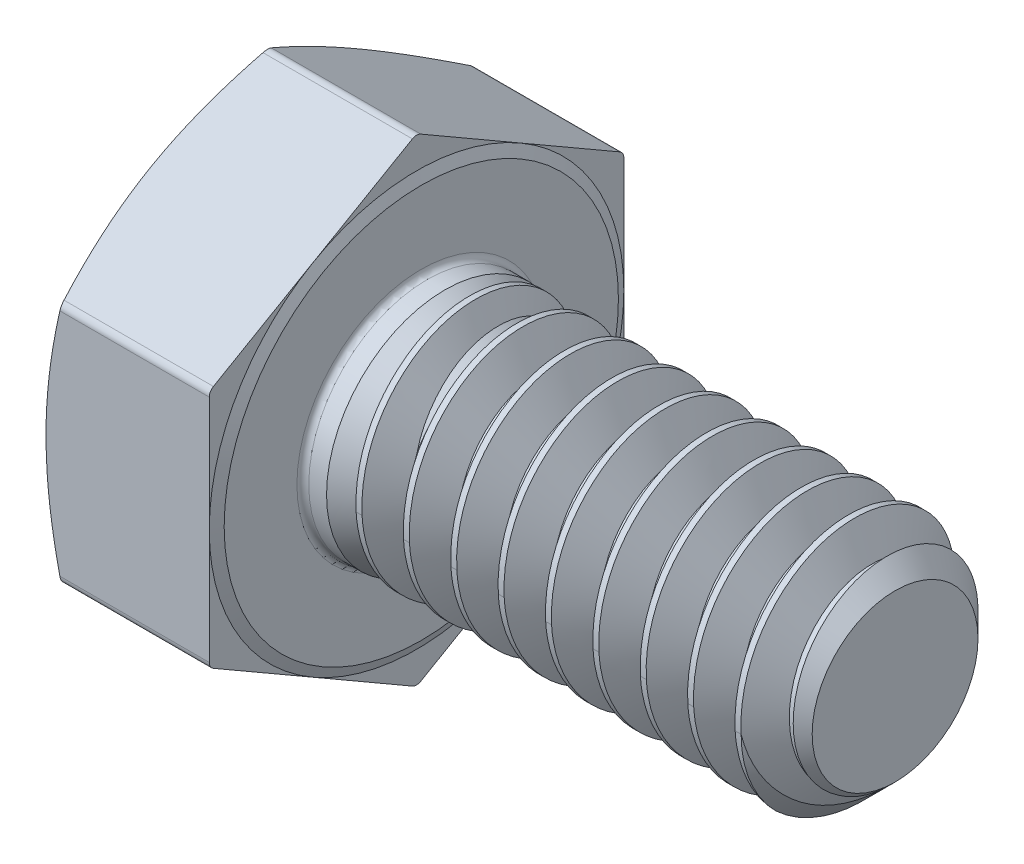
SolidWorks part; units mm, degrees
material "Plain Carbon Steel"
ref_plane "Front Plane" through (0, 0, 0) normal (0, 0, 1) x (1, 0, 0)
ref_plane "Top Plane" through (0, 0, 0) normal (0, 1, 0) x (1, 0, 0)
ref_plane "Right Plane" through (0, 0, 0) normal (1, 0, 0) x (0, 0, -1)
sketch "Sketch1" plane through (0, 0, 0) normal (0, 0, 1) x (1, 0, 0)
  line L0 (0, 0) -> (12.7, 0) construction
  line L1 (0, 0) -> (-4.7625, 0) construction
  line L2 (0, 5.5562) -> (0, -5.5562) construction
  line L3 (-4.7625, 5.5562) -> (-4.7625, -5.5563) construction
  line L4 (12.7, 3.175) -> (12.7, -3.175) construction
  line L8 (11.43, 3.175) -> (12.7, 3.175) construction
  point P8 (11.43, 0)
  point P11 (8.255, -3.175)
  point P12 (0.635, 0)
  dimension "Head Height" = 4.7625
  dimension "Head Width" = 11.1125
  dimension "Length" = 12.7
  dimension "Thread Size" = 6.35
  dimension "D1" = 4.445
  dimension "Thread Pitch" = 1.27
  dimension "D2" = 0.635
sketch "Sketch2" plane through (0, 0, 0) normal (1, 0, 0) x (0, 0, -1)
  circle A0 centre (0, 0) radius 3.175
extrude "Boss-Extrude1" add sketch "Sketch2" along normal up to vertex (12.7 mm away) up to point (12.7, 3.175, 0)
sketch "Sketch3" plane through (0, 0, 0) normal (-1, 0, 0) x (0, 0, 1)
  line L0 (0, 6.4158) -> (0, 0) construction
  line L1 (0, 6.4158) -> (-5.5563, 3.2079)
  line L2 (-5.5563, 3.2079) -> (-5.5562, -3.2079)
  line L3 (-5.5562, -3.2079) -> (0, -6.4158)
  line L4 (0, -6.4158) -> (5.5563, -3.2079)
  line L5 (5.5563, -3.2079) -> (5.5563, 3.2079)
  line L6 (5.5563, 3.2079) -> (0, 6.4158)
  circle A0 centre (0, 0) radius 5.5562 construction
extrude "Boss-Extrude2" add sketch "Sketch3" along normal up to vertex (4.7625 mm away) up to point (-4.7625, 5.5562, 0)
sketch "Sketch5" plane through (-4.7625, 0, 0) normal (-1, 0, 0) x (0, 0, 1)
  circle A0 centre (0, 0) radius 5.5562 construction
  circle A1 centre (0, 0) radius 5.5562 construction
  circle A2 centre (0, 0) radius 5.0006
  dimension "D1" = 0.5556
extrude "Cut-Extrude1" cut sketch "Sketch5" against normal up to vertex (4.7625 mm away) draft 65 flip side to cut up to point (0, 0, 0)
sketch "Sketch11" plane through (-4.7625, 0, 0) normal (-1, 0, 0) x (0, 0, 1)
  line L0 (0, 4.6672) -> (0, 2.9726) construction
  line L1 (0.1945, 4.6672) -> (0.1945, 2.9726)
  line L2 (-0.1945, 4.6672) -> (-0.1945, 2.9726)
  arc A0 (0.1945, 4.6672) -> (-0.1945, 4.6672) centre (0, 4.6672) ccw
  arc A1 (-0.1945, 2.9726) -> (0.1945, 2.9726) centre (0, 2.9726) ccw
  circle A2 centre (0, 0) radius 4.8617 construction
  circle A3 centre (0, 0) radius 2.7781 construction
  point P3 (0, 3.8199)
  dimension "D1" = 9.7234
  dimension "D2" = 5.5562
  dimension "D3" = 0.3889
extrude "Boss-Extrude5" add sketch "Sketch11" along normal blind 0.0635
fillet "Fillet5" radius 0.0635 4 edges at (-4.826, 3.8199, 0.1945) (-4.826, 2.7781, 0) (-4.826, 3.8199, -0.1945) (-4.826, 4.8617, 0)
fillet "Fillet6" radius 0.0635 4 edges at (-4.7625, 2.7781, 0) (-4.7625, 3.8199, -0.1945) (-4.7625, 4.8617, 0) (-4.7625, 3.8199, 0.1945)
pattern_circular "CirPattern1" count 9 over 360 about axis through (0, 0, 0) along (-1, 0, 0) of "Boss-Extrude5", "Fillet5", "Fillet6" reverse direction yes
sketch "Sketch16" plane through (-4.7625, 0, 0) normal (-1, 0, 0) x (0, 0, 1)
  circle A0 centre (0, 0) radius 2.5003
  dimension "D1" = 5.0006
extrude "Cut-Extrude2" cut sketch "Sketch16" against normal blind 0.508 draft 60
fillet "Fillet7" radius 0.2223 6 edges at (-2.0513, -6.4158, 0) (-2.0513, -3.2079, -5.5562) (-2.0513, 3.2079, -5.5563) (-2.0513, 6.4158, 0) (-2.0513, -3.2079, 5.5563) (-2.0513, 3.2079, 5.5563)
chamfer "Chamfer1" distance 0.9525 angle 45 1 edges at (12.7, 0, -3.175)
sketch "Sketch15" plane through (0, 0, 0) normal (0, 0, 1) x (1, 0, 0)
  line L0 (0, 5.2839) -> (-0.127, 5.5562)
  line L1 (0, 5.5562) -> (0, -5.5562) construction
  line L2 (-0.127, 5.5562) -> (-0.127, 6.4158)
  line L3 (-0.127, 6.4158) -> (0, 6.4158)
  line L4 (0, 6.4158) -> (0, 5.2839)
  dimension "D1" = 0.127
  dimension "D2" = 25
revolve "Cut-Revolve1" cut sketch "Sketch15" angle 360 about L1
fillet "Fillet4" radius 0.1588 1 edges at (0, 0, 3.175)
sketch "Reference Sketch1" plane through (0, 0, 0) normal (1, 0, 0) x (0, 0, -1)
  line L1 (0, 6.4158) -> (-5.5562, 3.2079)
  line L2 (-5.5562, 3.2079) -> (-5.5562, -3.2079)
  line L3 (-5.5562, -3.2079) -> (0, -6.4158)
  line L4 (0, -6.4158) -> (5.5562, -3.2079)
  line L5 (5.5562, -3.2079) -> (5.5562, 3.2079)
  line L6 (5.5562, 3.2079) -> (0, 6.4158)
  circle A0 centre (0, 0) radius 5.5562 construction
  circle A1 centre (0, 0) radius 5.5562
sketch "Sketch12" plane through (12.7, 0, 0) normal (1, 0, 0) x (0, 0, -1)
  circle A1 centre (0, 0) radius 3.175
ref_plane "Plane2" through (0.635, 0, 0) normal (1, 0, 0) x (0, 0, -1)
split "Split1" trim tools "Plane2" bodies to split 126 116 resulting bodies 118 119
curve "Helix/Spiral2" pitch 1.27 height 13.97 radius 3.175 centre (12.7, 0, 0) axis (-1, 0, 0) start towards (0, 1, 0) parameters "Pitch"=1.27
sketch "Sketch13" plane through (0, 0, 0) normal (0, 0, 1) x (1, 0, 0)
  line L0 (12.6206, 3.3125) -> (13.2556, 2.2126) construction
  line L1 (13.2556, 2.2126) -> (13.8906, 3.3125) construction
  line L2 (13.8906, 3.3125) -> (12.6206, 3.3125) construction
  line L3 (13.2556, 2.2126) -> (13.2556, 2.3501) construction
  line L4 (12.7, 3.175) -> (13.8112, 3.175)
  line L5 (13.2556, 3.175) -> (13.2556, 3.3125) construction
  line L6 (13.8112, 3.175) -> (13.335, 2.3501)
  line L7 (13.335, 2.3501) -> (13.1763, 2.3501)
  line L8 (13.1763, 2.3501) -> (12.7, 3.175)
  line L9 (11.43, 3.175) -> (12.7, 3.175) construction
  dimension "D1" = 0.1588
sweep "Cut-Sweep1" cut profiles "Sketch13" path "Helix/Spiral2" align with end faces yes
sketch "Sketch14" plane through (0.635, 0, 0) normal (1, 0, 0) x (0, 0, -1)
  circle A1 centre (0, 0) radius 3.175
  circle A2 centre (0, 0) radius 3.175
  dimension "D1" = 0
extrude "Boss-Extrude4" add sketch "Sketch14" along normal through all draft 31.8
equation "\"D1@Sketch11\"=\"Head Width@Sketch1\" * 0.875"
equation "\"D2@Sketch11\"=\"Head Width@Sketch1\"*0.5"
equation "\"D3@Sketch11\"=\"Head Width@Sketch1\" * .035"
equation "\"D3@Helix/Spiral2\"=\"Length@Sketch1\" + \"Thread Pitch@Sketch1\""
equation "\"D1@Chamfer1\"=\"Thread Pitch@Sketch1\"*0.750"
equation "\"D1@Sketch1\"=\"Thread Pitch@Sketch1\"*3.5"
equation "\"Pitch@Helix/Spiral2\"=\"Thread Pitch@Sketch1\""
equation "\"D1@Sketch13\"=\"Thread Pitch@Sketch1\"*0.125"
equation "\"D1@Sketch5\"=\"Head Width@Sketch1\"*0.05"
equation "\"D1@Fillet4\"=\"Thread Size@Sketch1\"*0.025"
equation "\"D2@Sketch1\"=\"Thread Pitch@Sketch1\"*0.5"
equation "\"D1@Fillet7\"=\"Head Width@Sketch1\"*0.02"
equation "\"D1@Sketch16\"=\"Head Width@Sketch1\"*0.45"
